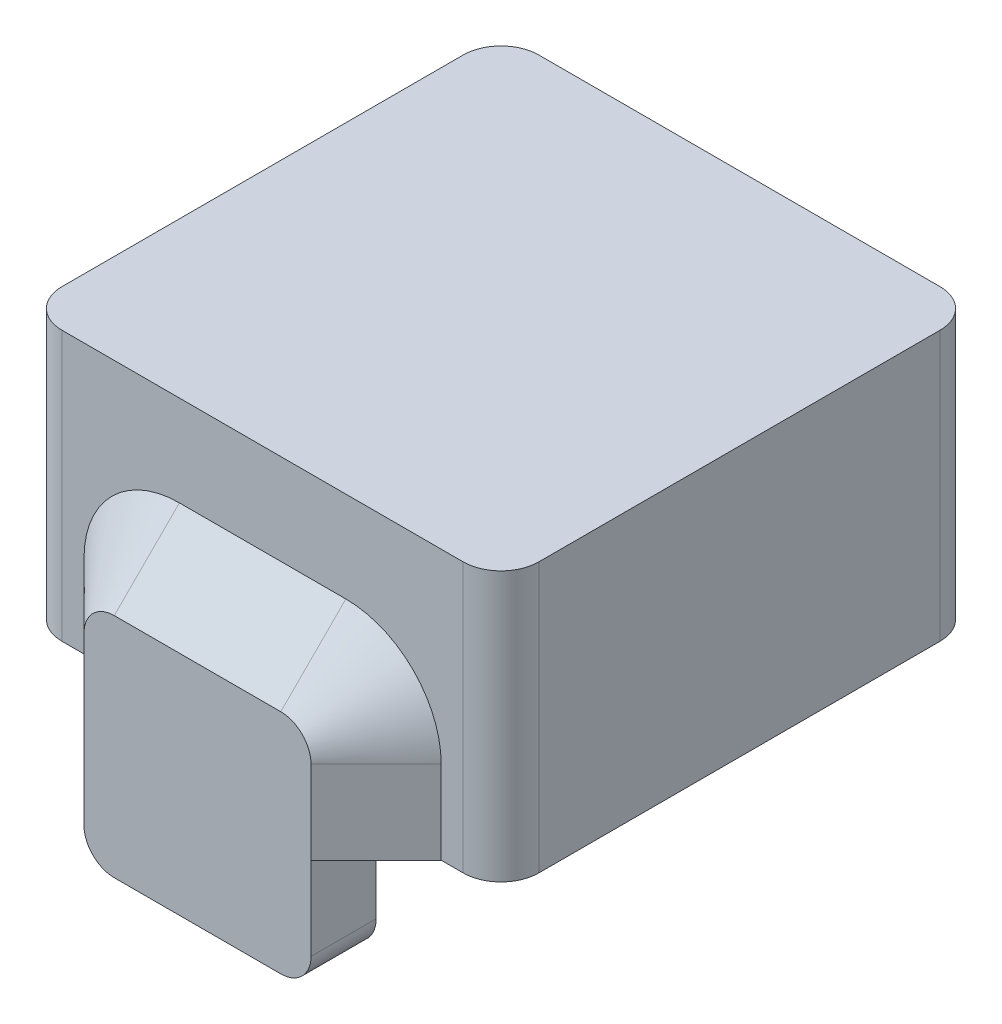
SolidWorks part; units mm, degrees
ref_plane "Front Plane" through (0, 0, 0) normal (0, 0, 1) x (1, 0, 0)
ref_plane "Top Plane" through (0, 0, 0) normal (0, 1, 0) x (1, 0, 0)
ref_plane "Right Plane" through (0, 0, 0) normal (1, 0, 0) x (0, 0, -1)
sketch "Sketch1" plane through (0, 0, 0) normal (0, 1, 0) x (1, 0, 0)
  line L0 (0, 0) -> (-3.15, 0) construction
  line L1 (-3.15, -3.15) -> (3.15, -3.15)
  line L2 (-3.15, -3.15) -> (-3.15, 3.15)
  line L3 (-3.15, 3.15) -> (3.15, 3.15)
  line L4 (3.15, -3.15) -> (3.15, 3.15)
  line L5 (-3.15, -3.15) -> (3.15, 3.15) construction
  line L6 (-3.15, 3.15) -> (3.15, -3.15) construction
  line L7 (-1.5, 3.15) -> (1.5, 3.15)
  line L8 (-1.5, 3.15) -> (-1.5, 4.01)
  line L9 (-1.5, 4.01) -> (1.5, 4.01)
  line L10 (1.5, 3.15) -> (1.5, 4.01)
  line L11 (-1.5, -3.15) -> (-1.5, -4.01)
  line L12 (-1.5, -3.15) -> (1.5, -3.15)
  line L13 (1.5, -3.15) -> (1.5, -4.01)
  line L14 (-1.5, -4.01) -> (1.5, -4.01)
  circle A0 centre (0, 0) radius 1.625
  circle A1 centre (0, 0) radius 1.1
  point P0 (0, 0)
  point P18 (0, 4.01)
  dimension "D2" = 2.2
  dimension "D3" = 3.25
  dimension "D1" = 6.3
  dimension "D4" = 3
  dimension "D5" = 0.86
extrude "Boss-Extrude1" add sketch "Sketch1" along normal blind 3.5599 contours L1 L4 L3 L2 A0 | A0 A1 | A1 region at (-3.0609, 0, 0) region at (-1.579, 0, 0) region at (0, 0, 0)
extrude "Cut-Extrude1" cut sketch "Sketch1<3>" along normal blind 2.6 contours A0 A1 region at (-1.579, 0, 0)
sketch "Sketch1<3>" plane through (0, 0, 0) normal (0, 1, 0) x (1, 0, 0) same geometry as "Sketch1"
extrude "Boss-Extrude2" add sketch "Sketch1<4>" along normal mid plane 3 contours L11 L14 L13 L1 | L3 L10 L9 L8 region at (0, 0, 3.58) region at (0, 0, -3.58)
sketch "Sketch1<4>" plane through (0, 0, 0) normal (0, 1, 0) x (1, 0, 0) same geometry as "Sketch1"
fillet "Fillet1" radius 0.4 8 edges at (1.5, 1.5, -3.58) (-1.5, 1.5, -3.58) (1.5, 1.5, 3.58) (-1.5, 1.5, 3.58) (-1.5, -1.5, -3.58) (1.5, -1.5, -3.58) (1.5, -1.5, 3.58) (-1.5, -1.5, 3.58)
chamfer "Chamfer1" distance 0.86 angle 45 10 edges at (-1.5, 0.55, 3.15) (1.5, 0.55, 3.15) (-1.3828, 1.3828, 3.15) (1.3828, 1.3828, 3.15) (0, 1.5, 3.15) (-1.5, 0.55, -3.15) (1.5, 0.55, -3.15) (-1.3828, 1.3828, -3.15) (1.3828, 1.3828, -3.15) (0, 1.5, -3.15)
fillet "Fillet2" radius 0.5 4 edges at (-3.15, 1.78, -3.15) (3.15, 1.78, -3.15) (3.15, 1.78, 3.15) (-3.15, 1.78, 3.15)
extrude "Cut-Extrude2" cut sketch "Sketch1<5>" along normal blind 2.9599 contours A1 region at (0, 0, 0)
sketch "Sketch1<5>" plane through (0, 0, 0) normal (0, 1, 0) x (1, 0, 0) same geometry as "Sketch1"
